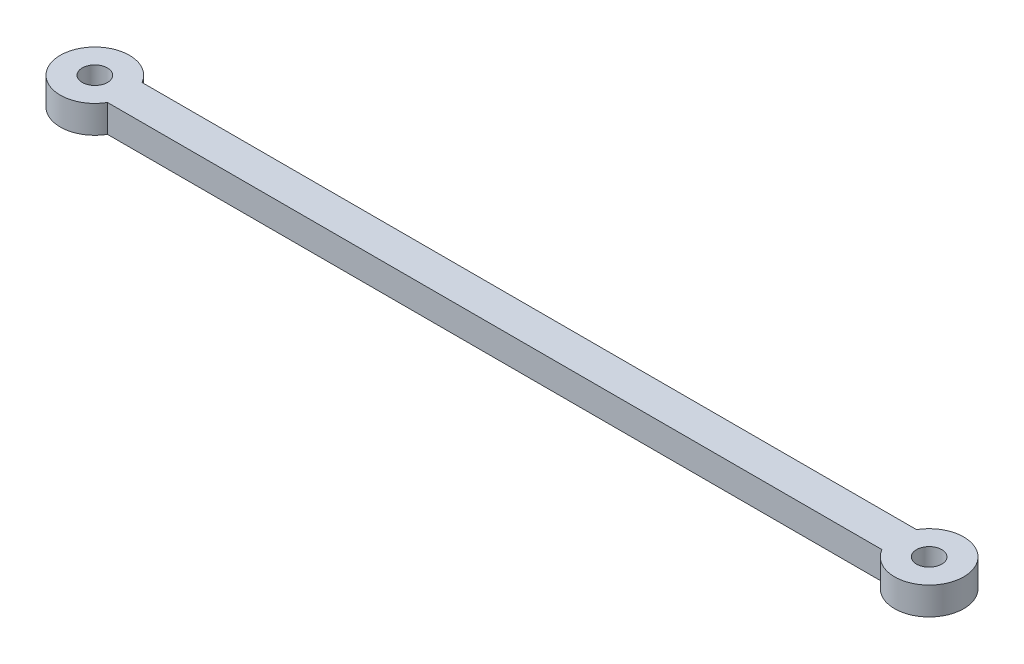
SolidWorks part; units mm, degrees
ref_plane "Front Plane" through (0, 0, 0) normal (0, 0, 1) x (1, 0, 0)
ref_plane "Top Plane" through (0, 0, 0) normal (0, 1, 0) x (1, 0, 0)
ref_plane "Right Plane" through (0, 0, 0) normal (1, 0, 0) x (0, 0, -1)
sketch "Sketch1" plane through (0, 0, 0) normal (0, 1, 0) x (1, 0, 0)
  line L0 (-56, 2.5) -> (56, 2.5)
  line L1 (-56, -2.5) -> (56, -2.5)
  line L2 (-55, 0) -> (55, 0) construction
  arc A1 (-56, 2.5) -> (-56, -2.5) centre (-60.3301, 0) ccw
  arc A2 (56, 2.5) -> (56, -2.5) centre (60.3301, 0) cw
  dimension "D2" = 56
  dimension "D3" = 5
  dimension "D7" = 5
  dimension "D1" = 5
  dimension "D4" = 112
  dimension "D5" = 112
  dimension "D6" = 2.5
extrude "Boss-Extrude1" add sketch "Sketch1" along normal blind 4
sketch "Sketch2" plane through (0, 4, 0) normal (0, 1, 0) x (1, 0, 0)
  circle A0 centre (-60.3301, 0) radius 1.825
  circle A1 centre (60.3301, 0) radius 1.825
  dimension "D1" = 3.65
  dimension "D2" = 3.65
extrude "Cut-Extrude1" cut sketch "Sketch2" against normal through all
